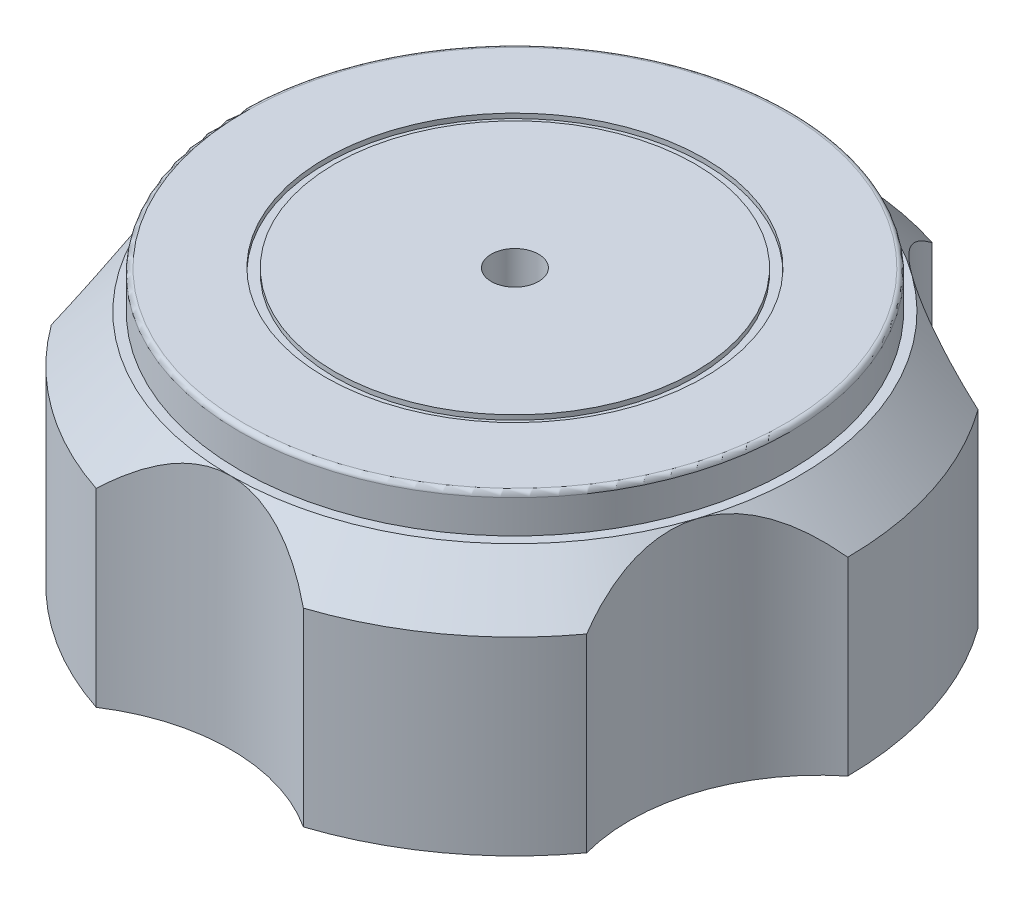
SolidWorks part; units mm, degrees
ref_plane "Front Plane" through (0, 0, 0) normal (0, 0, 1) x (1, 0, 0)
ref_plane "Top Plane" through (0, 0, 0) normal (0, 1, 0) x (1, 0, 0)
ref_plane "Right Plane" through (0, 0, 0) normal (1, 0, 0) x (0, 0, -1)
sketch "Sketch1" plane through (0, 0, 0) normal (0, 1, 0) x (1, 0, 0)
  circle A0 centre (0, 0) radius 35
  circle A2 centre (0, -50) radius 20
  circle A3 centre (47.5528, -15.4508) radius 20
  circle A4 centre (29.3893, 40.4508) radius 20
  circle A5 centre (-29.3893, 40.4508) radius 20
  circle A6 centre (-47.5528, -15.4508) radius 20
  dimension "D1" = 70
  dimension "D9" = 40
  dimension "D14" = 40
  dimension "D15" = 40
  dimension "D16" = 40
  dimension "D17" = 40
  dimension "D8" = 50
  dimension "D10" = 50
  dimension "D11" = 50
  dimension "D12" = 50
  dimension "D13" = 50
extrude "Boss-Extrude2" add sketch "Sketch1" along normal blind 25 contours A6 A0 A2 A3 A4 A5 region at (0, 0, 0)
fillet "Fillet6" radius 5 5 edges at (-33.287, 25, -10.8156) (0, 25, -35) (33.287, 25, -10.8156) (20.5725, 25, 28.3156) (-20.5725, 25, 28.3156) profile chamfer
sketch "Sketch4" plane through (0, 0, 0) normal (0, -1, 0) x (-1, 0, 0)
  circle A1 centre (0, 0) radius 25
  circle A2 centre (0, 0) radius 5
  circle A3 centre (0, 0) radius 2.6
  dimension "D1" = 5.2
  dimension "D2" = 50
  dimension "D3" = 10
extrude "Cut-Extrude1" cut sketch "Sketch4" against normal blind 20 contours A1 A2 region at (24.2929, 0, 0)
extrude "Cut-Extrude2" cut sketch "Sketch4<3>" against normal blind 20 contours A3 region at (0, 0, 0)
sketch "Sketch4<3>" plane through (0, 0, 0) normal (0, -1, 0) x (-1, 0, 0) same geometry as "Sketch4"
thread "Thread1" pitch 1.5 method extrude trim with start face yes trim with end face yes profile "Thread Profile1" start angle 0, offset 1.5, length 21.5, pitch 1.5, diameter 50
ref_plane "Plane3" through (25, -1.5, 0) normal (0, 0, 1) x (1, 0, 0)
sketch "Thread Profile1" plane through (25, -1.5, 0) normal (0, 0, 1) x (1, 0, 0)
  line L0 (0, 0) -> (0, 1.5) construction
  line L11 (0, 0) -> (0, 1.3125)
  line L12 (0, 1.3125) -> (-0.8119, 0.8437)
  line L13 (-0.8119, 0.8437) -> (-0.8119, 0.4687)
  line L15 (-0.8119, 0.4687) -> (0, 0)
  line L17 (-0.8119, 0.6562) -> (0, 0.6562) construction
  point P2 (0, 0)
  dimension "Pitch" = 1.5
  dimension "Profile_Angle" = 60
  dimension "Profile_Land" = 0.375
  dimension "Profile_Height" = 0.8119
sketch "Sketch7" plane through (0, 25, 0) normal (0, 1, 0) x (1, 0, 0)
  circle A0 centre (0, 0) radius 29
  dimension "D1" = 58
extrude "Boss-Extrude4" add sketch "Sketch7" along normal blind 4
sketch "Sketch8" plane through (0, 29, 0) normal (0, 1, 0) x (1, 0, 0)
  circle A0 centre (0, 0) radius 20
  circle A1 centre (0, 0) radius 19
  dimension "D1" = 40
  dimension "D2" = 38
extrude "Cut-Extrude3" cut sketch "Sketch8" against normal blind 0.5
fillet "Fillet7" radius 0.5 1 edges at (0, 29, 29) type face fillet first side face at (0, 29, 20) second side face at (0, 29, 29)
sketch "Sketch9" plane through (0, 29, 0) normal (0, 1, 0) x (1, 0, 0)
  circle A0 centre (0, 0) radius 2.5
  dimension "D1" = 5
extrude "Cut-Extrude4" cut sketch "Sketch9" against normal blind 10
